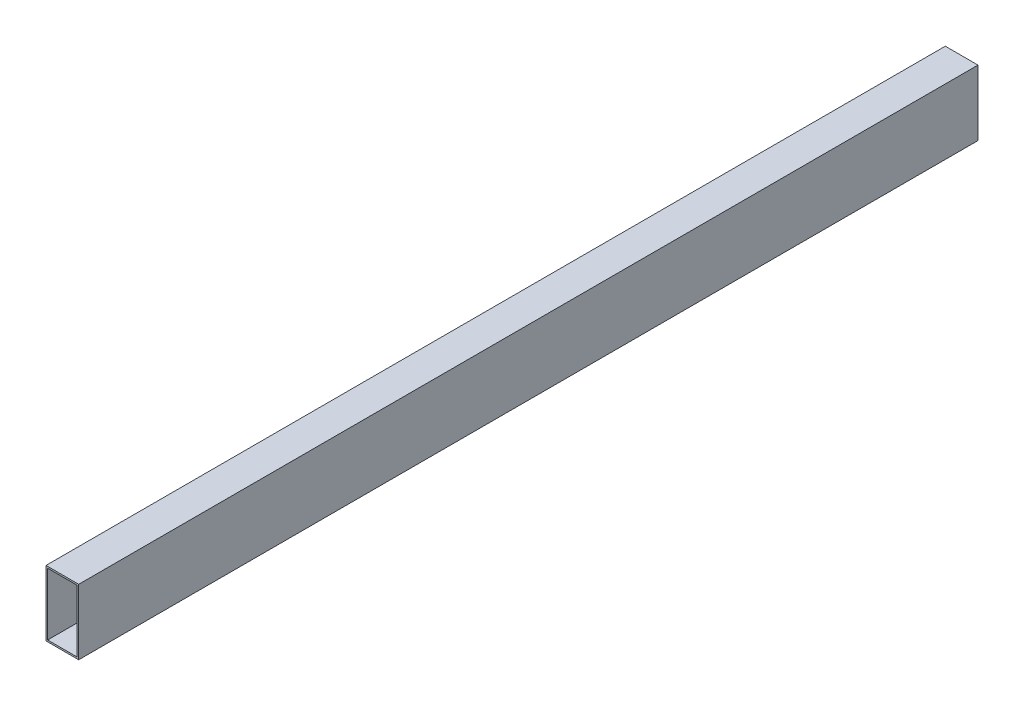
SolidWorks part; units mm, degrees
material "1060 合金"
ref_plane "前视基准面" through (0, 0, 0) normal (0, 0, 1) x (1, 0, 0)
ref_plane "上视基准面" through (0, 0, 0) normal (0, 1, 0) x (1, 0, 0)
ref_plane "右视基准面" through (0, 0, 0) normal (1, 0, 0) x (0, 0, -1)
other "Configuration Table"
sketch "草图1" plane through (0, 0, 0) normal (0, 0, 1) x (1, 0, 0)
  line L1 (0, 0) -> (20, 0)
  line L2 (0, 0) -> (0, -40)
  line L3 (0, -40) -> (20, -40)
  line L4 (20, 0) -> (20, -40)
  dimension "D1" = 40
  dimension "D2" = 20
extrude "拉伸-薄壁1" add sketch "草图1" along normal blind 550 thin thin type one direction reverse wall 1
